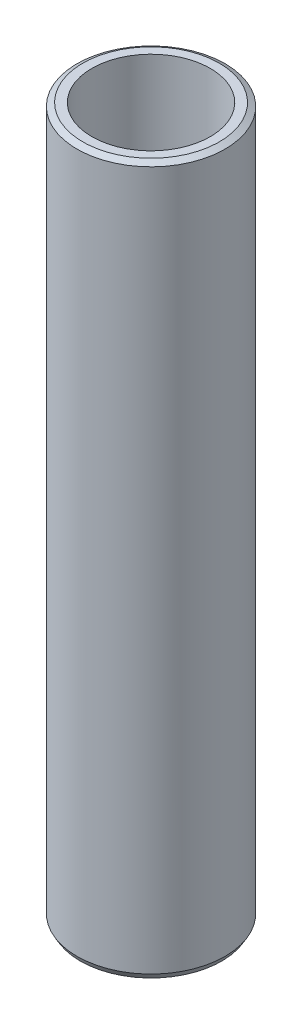
SolidWorks part; units mm, degrees
ref_plane "Front Plane" through (0, 0, 0) normal (0, 0, 1) x (1, 0, 0)
ref_plane "Top Plane" through (0, 0, 0) normal (0, 1, 0) x (1, 0, 0)
ref_plane "Right Plane" through (0, 0, 0) normal (1, 0, 0) x (0, 0, -1)
sketch "Sketch1" plane through (0, 0, 0) normal (0, 1, 0) x (1, 0, 0)
  circle A0 centre (0, 0) radius 25
  dimension "SHAFT_OD" = 50
extrude "Boss-Extrude1" add sketch "Sketch1" along normal blind 239.1346
sketch "Sketch2" plane through (0, 0, 0) normal (0, 1, 0) x (1, 0, 0)
  circle A0 centre (0, 0) radius 19.9933
  dimension "BORE_D" = 39.9866
extrude "Cut-Extrude1" cut sketch "Sketch2" along normal through all
chamfer "Chamfer1" distance 1.1312 angle 60 2 edges at (0, 239.1346, 25) (0, 0, 25) first distance on face at (0, 239.1346, 25) first distance on face at (0, 0, 19.9933)
